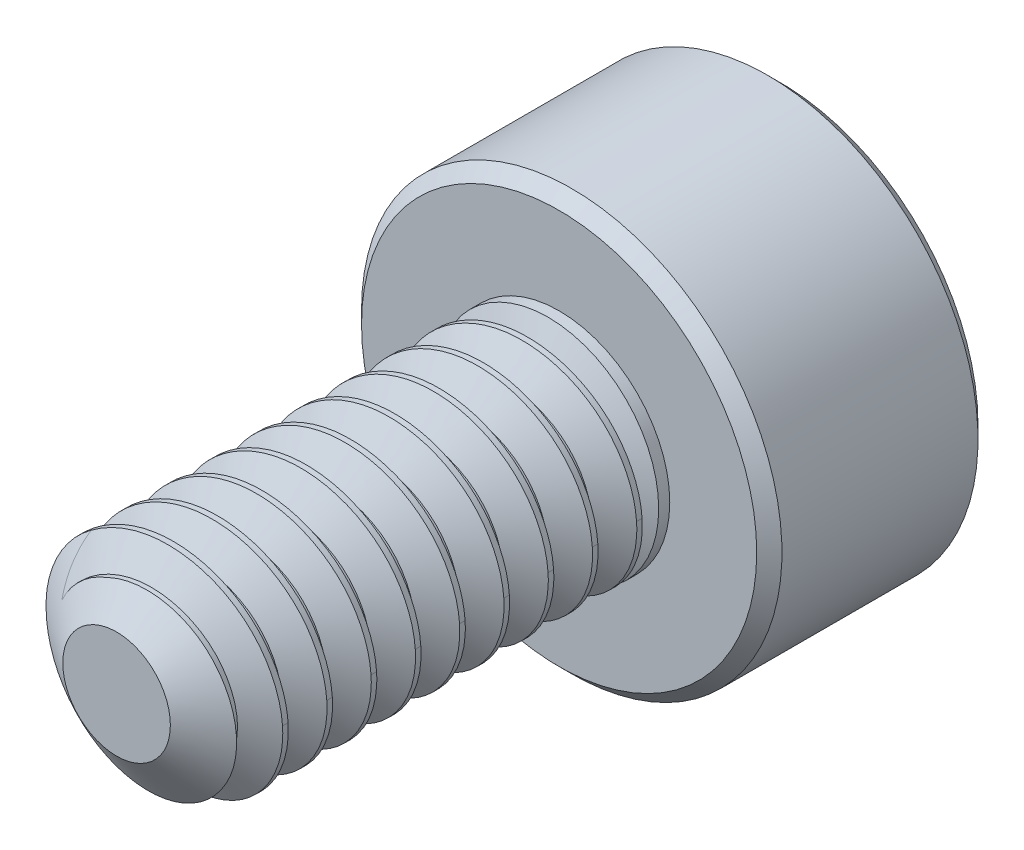
SolidWorks part; units mm, degrees
ref_plane "Front Plane" through (0, 0, 0) normal (0, 0, 1) x (1, 0, 0)
ref_plane "Top Plane" through (0, 0, 0) normal (0, 1, 0) x (1, 0, 0)
ref_plane "Right Plane" through (0, 0, 0) normal (1, 0, 0) x (0, 0, -1)
sketch "Sketch1" plane through (0, 0, 0) normal (0, 0, 1) x (1, 0, 0)
  circle A0 centre (0, 0) radius 1
  dimension "OD" = 2
extrude "Extrude1" add sketch "Sketch1" against normal blind 4
sketch "Sketch2" plane through (0, 0, 0) normal (0, 0, 1) x (1, 0, 0)
  circle A0 centre (0, 0) radius 1 construction
  circle A1 centre (0, 0) radius 1
curve "Helix/Spiral1" pitch 0.4 height 4.4 radius 1 centre (0, 0, 0) axis (0, 0, -1) start towards (0, 1, 0) parameters "pitch"=0.4
sketch "Sketch3" plane through (0, 0, 0) normal (1, 0, 0) x (0, 0, -1)
  line L0 (-0.35, 1) -> (-0.2, 0.7402)
  line L1 (-0.2, 0.7402) -> (-0.15, 0.7402)
  line L2 (-0.15, 0.7402) -> (0, 1)
  line L3 (-0.35, 1) -> (0, 1)
  line L4 (-0.175, 1) -> (-0.175, 0.7402) construction
  line L5 (-0.275, 0.8701) -> (-0.075, 0.8701) construction
  line L6 (0, 1) -> (0, -1) construction
  line L7 (0, -1) -> (4, -1) construction
  point P11 (1.8, -1)
  dimension "D1" = 0.05
  dimension "D2" = 0.2
  dimension "D3" = 60
  dimension "D4" = 1.8
sweep "Cut-Sweep1" cut profiles "Sketch3" path "Helix/Spiral1"
sketch "Sketch4" plane through (0, 0, 0) normal (1, 0, 0) x (0, 0, -1)
  line L0 (0.3598, 1) -> (0, 0.4862)
  line L1 (0, 0.4862) -> (0, 1)
  line L2 (0.3598, 1) -> (0, 1)
  line L3 (-0.35, 1) -> (0, 1) construction
  line L4 (0, 0) -> (7.0209, 0) construction
  dimension "D1" = 55
  dimension "D2" = 0.254
revolve "Cut-Revolve1" cut sketch "Sketch4" angle 360 about L4
sketch "Sketch5" plane through (0, 0, 0) normal (1, 0, 0) x (0, 0, -1)
  line L0 (4, -0.7473) -> (4, 0.7135) construction
  line L1 (4, 1) -> (0.1203, 1)
  line L2 (4, 1) -> (4, 0)
  line L3 (4, 0) -> (0.0001, 0)
  line L4 (0.0001, 0.6698) -> (0.0001, 0)
  line L5 (0.1203, 1) -> (0.0001, 0.6698)
  line L6 (0, 0) -> (9.9695, 0) construction
  point P3 (0.0001, 1)
  point P10 (0.0001, 1)
  dimension "D1" = 0.3302
  dimension "Thread min" = 0.0001
  dimension "D3" = 20
revolve "partially thread" [suppressed] add sketch "Sketch5" angle 360 about L6
sketch "Sketch6" plane through (0, 0, -4) normal (0, 0, -1) x (-1, 0, 0)
  circle A0 centre (0, 0) radius 1.9
  dimension "head dia" = 3.8
extrude "Extrude2" add sketch "Sketch6" along normal blind 2
sketch "Sketch7" plane through (0, 0, -6) normal (0, 0, -1) x (-1, 0, 0)
  line L1 (0, 0.866) -> (-0.75, 0.433)
  line L2 (-0.75, 0.433) -> (-0.75, -0.433)
  line L3 (-0.75, -0.433) -> (0, -0.866)
  line L4 (0, -0.866) -> (0.75, -0.433)
  line L5 (0.75, -0.433) -> (0.75, 0.433)
  line L6 (0.75, 0.433) -> (0, 0.866)
  circle A0 centre (0, 0) radius 0.75 construction
  dimension "hex dia" = 1.5
extrude "Cut-Extrude1" cut sketch "Sketch7" against normal blind 1.125
sketch "Sketch8" plane through (0, 0, -6) normal (0, 0, -1) x (-1, 0, 0)
  circle A0 centre (0, 0) radius 0.866
extrude "Cut-Extrude2" cut sketch "Sketch8" against normal through all draft 45
chamfer "Chamfer1" distance 0.114 angle 45 2 edges at (-1.9, 0, -6) (-1.9, 0, -4)
sketch "Sketch9" plane through (0, 0, 0) normal (1, 0, 0) x (0, 0, -1)
  line L0 (0, 1) -> (0, -1) construction
  line L1 (2.2, 1) -> (2.2, -1) construction
  dimension "D1" = 2.2
sketch "Sketch10" plane through (0, 0, 0) normal (1, 0, 0) x (0, 0, -1)
  line L0 (4, 1) -> (4, 0)
  line L1 (4, 1) -> (3.9, 1)
  line L2 (3.9, 1) -> (3.4858, 0)
  line L3 (4, 0) -> (3.4858, 0)
  line L4 (4, 1.786) -> (4, -1.786) construction
  dimension "D1" = 22.5
  dimension "D2" = 0.1
revolve "Revolve1" add sketch "Sketch10" angle 360 about L3
equation "\"D3@Helix/Spiral1\" = \"screw length@Extrude1\"+\"pitch@Helix/Spiral1\""
equation "\"D1@Sketch3\" = \"pitch@Helix/Spiral1\"*.125"
equation "\"D2@Sketch3\" = \"pitch@Helix/Spiral1\"*.5"
equation "\"D1@Cut-Extrude1\" = \"hex dia@Sketch7\"*.75"
equation "\"D1@Chamfer1\" = \"head dia@Sketch6\"*.03"
equation "\"D1@Sketch9\" = \"pitch@Helix/Spiral1\"*5.5"
equation "\"D2@Sketch10\" = \"pitch@Helix/Spiral1\"*.25"
equation "\"D4@Sketch3\" = \"pitch@Helix/Spiral1\"*4.50"
